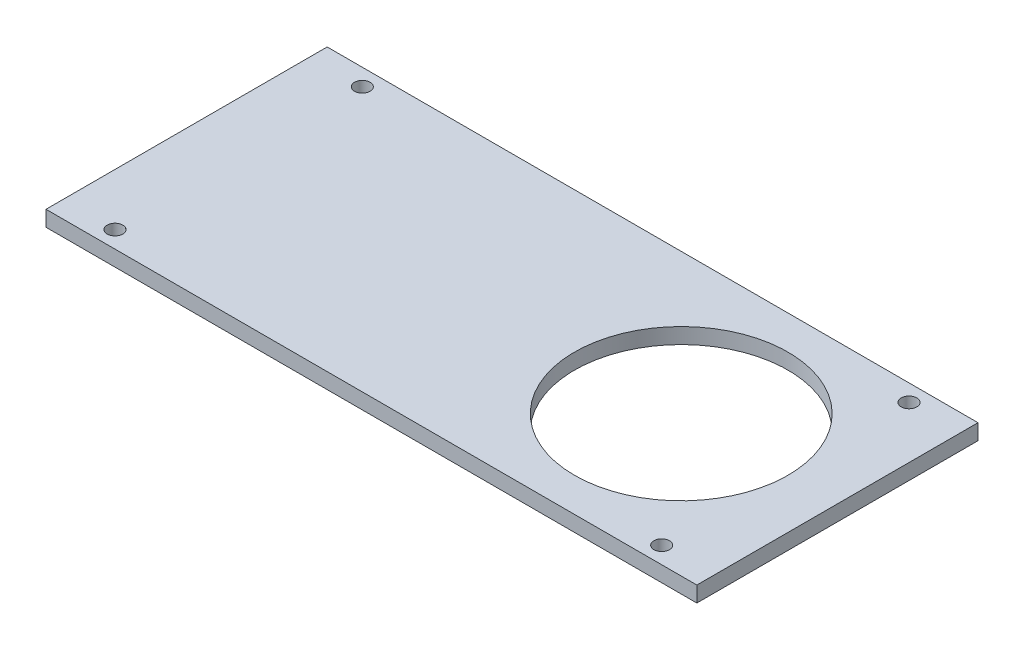
SolidWorks part; units mm, degrees
material "Сталь 3 ГОСТ 535-88"
ref_plane "Спереди" through (0, 0, 0) normal (0, 0, 1) x (1, 0, 0)
ref_plane "Сверху" through (0, 0, 0) normal (0, 1, 0) x (1, 0, 0)
ref_plane "Справа" through (0, 0, 0) normal (1, 0, 0) x (0, 0, -1)
sketch "Эскиз1" plane through (0, 0, 0) normal (0, 1, 0) x (1, 0, 0)
  line L1 (-125, -54) -> (125, -54)
  line L2 (-125, -54) -> (-125, 54)
  line L3 (-125, 54) -> (125, 54)
  line L4 (125, -54) -> (125, 54)
  line L5 (0, 54) -> (0, -54) construction
  line L6 (-125, 0) -> (125, 0) construction
  circle A0 centre (65, 0) radius 41
  point P0 (0, 0)
  dimension "D3" = 82
  dimension "D1" = 250
  dimension "D2" = 108
  dimension "D4" = 60
extrude "Бобышка-Вытянуть1" add sketch "Эскиз1" along normal blind 6
sketch "Эскиз2" plane through (0, 6, 0) normal (0, 1, 0) x (1, 0, 0)
  circle A0 centre (-105, -47.5) radius 3 construction
  circle A1 centre (-105, 47.5) radius 3 construction
  circle A2 centre (105, 47.5) radius 3 construction
  circle A3 centre (105, -47.5) radius 3 construction
  circle A4 centre (-105, -47.5) radius 3
  circle A5 centre (-105, 47.5) radius 3
  circle A6 centre (105, 47.5) radius 3
  circle A7 centre (105, -47.5) radius 3
extrude "Вырез-Вытянуть1" cut sketch "Эскиз2" against normal through all
